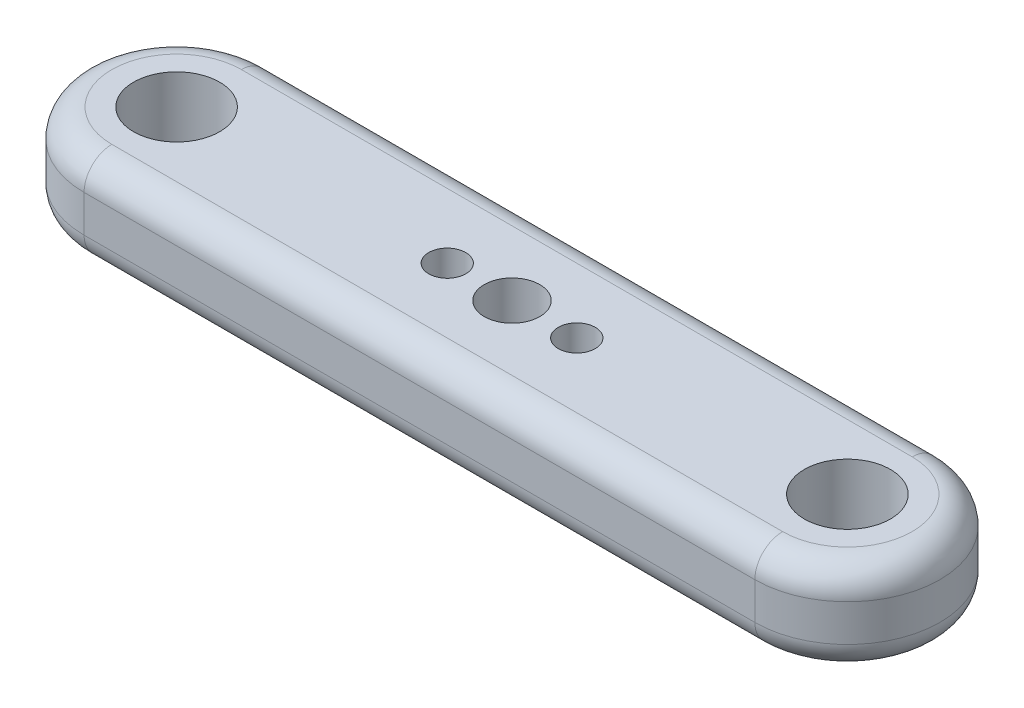
SolidWorks part; units mm, degrees
ref_plane "Front Plane" through (0, 0, 0) normal (0, 0, 1) x (1, 0, 0)
ref_plane "Top Plane" through (0, 0, 0) normal (0, 1, 0) x (1, 0, 0)
ref_plane "Right Plane" through (0, 0, 0) normal (1, 0, 0) x (0, 0, -1)
sketch "Sketch2" plane through (0, 0, 0) normal (0, 1, 0) x (1, 0, 0)
  line L4 (-36.25, 10) -> (36.25, 10)
  line L10 (36.25, -10) -> (-36.25, -10)
  arc A1 (0, -5) -> (0, 5) centre (0, 0) ccw
  circle A5 centre (0, 0) radius 5
  circle A6 centre (-36.25, 0) radius 5
  circle A7 centre (36.25, 0) radius 5
  arc A8 (-36.25, 10) -> (-36.25, -10) centre (-36.25, 0) ccw
  arc A9 (36.25, -10) -> (36.25, 10) centre (36.25, 0) ccw
  circle A10 centre (-36.25, 0) radius 10 construction
  circle A11 centre (36.25, 0) radius 10 construction
  point P3 (-19.375, 0)
  dimension "D1" = 5
  dimension "D2" = 5
extrude "Boss-Extrude1" add sketch "Sketch2" along normal blind 10 contours L10 A9 L4 A8 A5 A1 A6 A7 region at (0, 0, -9.0536)
fillet "Fillet1" radius 3 8 edges at (-46.25, 0, 0) (0, 0, 10) (46.25, 0, 0) (-46.25, 10, 0) (0, 10, 10) (46.25, 10, 0) (0, 0, -10) (0, 10, -10)
sketch "Sketch3" plane through (0, 10, 0) normal (0, 1, 0) x (1, 0, 0)
  line L0 (0, 0) -> (-6.5, 0)
  line L1 (-6.5, 0) -> (7.6495, 0)
  circle A0 centre (0, 0) radius 5
  circle M5 centre (0, 0) radius 5
extrude "Boss-Extrude2" add sketch "Sketch3" against normal blind 10 contours L0 L1 M5 | L1 L0 M5 region at (0, 10, 2.1221) region at (0, 10, -2.1221)
sketch "Sketch4" plane through (0, 10, 0) normal (0, 1, 0) x (1, 0, 0)
  line L0 (0, 0) -> (-8.2, 0)
  line L1 (0, 0) -> (8.2, 0)
  circle A0 centre (-8.2, 0) radius 1.5
  circle A1 centre (8.2, 0) radius 1.5
sketch "Sketch5" plane through (0, 10, 0) normal (0, 1, 0) x (1, 0, 0)
  circle A0 centre (-36.25, 0) radius 4.5
  circle A1 centre (-36.25, 0) radius 5
  circle A2 centre (36.25, 0) radius 5
  circle A3 centre (36.25, 0) radius 4.5
extrude "Boss-Extrude3" add sketch "Sketch5" against normal up to surface (10 mm away) up to face at (0, 0, 0)
sketch "Sketch6" plane through (0, 10, 0) normal (0, 1, 0) x (1, 0, 0)
  line L0 (7, 0) -> (-7, 0)
  circle A1 centre (-7, 0) radius 2
  circle A2 centre (7, 0) radius 2
extrude "Cut-Extrude1" cut sketch "Sketch6" against normal blind 10 contours A1 | A2 region at (-8.9434, 10, 0) region at (7, 10, -1.9434)
sketch "Sketch7" plane through (0, 10, 0) normal (0, 1, 0) x (1, 0, 0)
  circle A0 centre (0, 0) radius 3
extrude "Cut-Extrude2" cut sketch "Sketch7" against normal blind 10
sketch "Sketch8" plane through (0, 10, 0) normal (0, 1, 0) x (1, 0, 0)
  circle A0 centre (-36.25, 0) radius 4.65
  circle A1 centre (36.25, 0) radius 4.65
extrude "Cut-Extrude3" cut sketch "Sketch8" against normal blind 17
